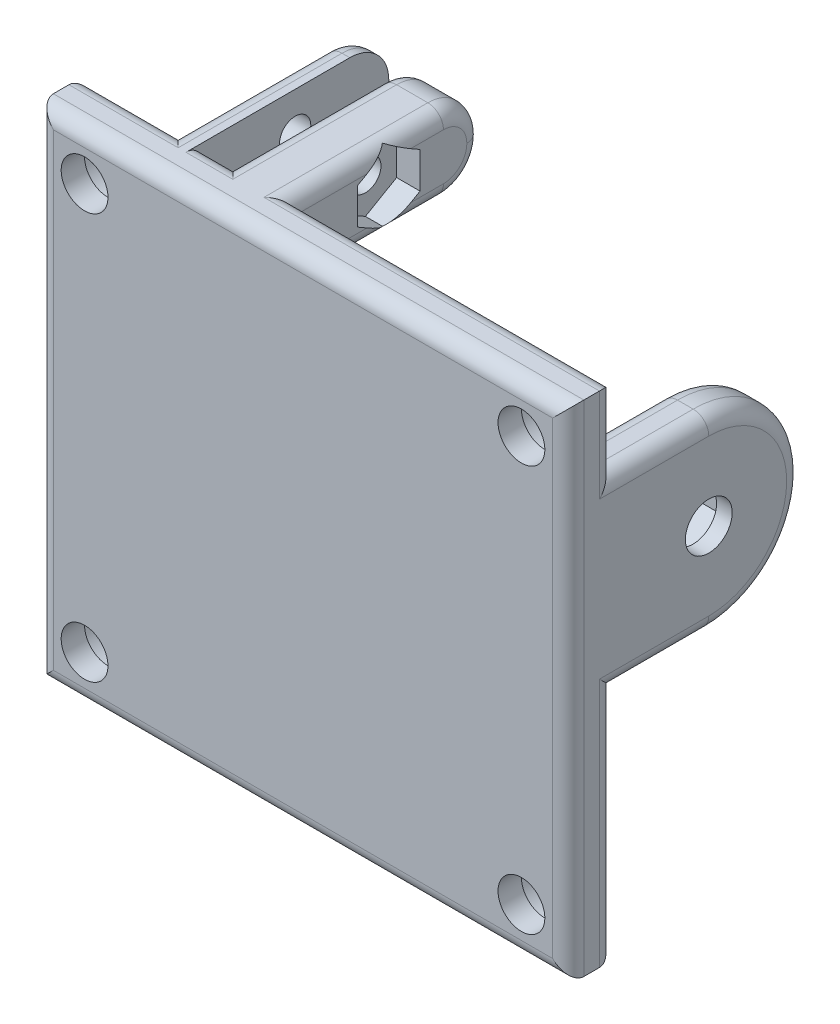
SolidWorks part; units mm, degrees
ref_plane "前视基准面" through (0, 0, 0) normal (0, 0, 1) x (1, 0, 0)
ref_plane "上视基准面" through (0, 0, 0) normal (0, 1, 0) x (1, 0, 0)
ref_plane "右视基准面" through (0, 0, 0) normal (1, 0, 0) x (0, 0, -1)
sketch "草图2" plane through (0, 0, 0) normal (0, 0, 1) x (1, 0, 0)
  line L0 (17, -17) -> (17, 17)
  line L1 (11, -11) -> (-11, -11)
  line L2 (11, -11) -> (11, 11)
  line L3 (11, 11) -> (-11, 11)
  line L4 (-11, -11) -> (-11, 11)
  line L5 (11, -11) -> (-11, 11) construction
  line L6 (11, 11) -> (-11, -11) construction
  line L7 (17, 17) -> (-17, 17)
  line L8 (-17, -17) -> (-17, 17)
  line L9 (17, -17) -> (-17, -17)
  point P0 (0, 0)
  dimension "D1" = 22
  dimension "D2" = 22
  dimension "D3" = 6
extrude "凸台-拉伸2" add sketch "草图2" along normal blind 12
sketch "草图3" plane through (0, 0, 12) normal (0, 0, 1) x (1, 0, 0)
  line L1 (-17, 17) -> (17, 17)
  line L2 (-17, 17) -> (-17, -17)
  line L3 (-17, -17) -> (17, -17)
  line L4 (17, 17) -> (17, -17)
  dimension "D1" = 34
extrude "凸台-拉伸3" add sketch "草图3" along normal blind 3
sketch "草图5" plane through (0, 0, 0) normal (0, 0, -1) x (-1, 0, 0)
  line L1 (-17, 11) -> (17, 11)
  line L2 (-17, 11) -> (-17, -3.5)
  line L3 (-17, -3.5) -> (17, -3.5)
  line L4 (17, 11) -> (17, -3.5)
  line L6 (-17, -17) -> (-17, 17) construction
  line L7 (17, 17) -> (17, -17) construction
  line L9 (-11, 11) -> (11, 11) construction
  dimension "D1" = 14.5
  dimension "D2" = 34
extrude "切除-拉伸1" cut sketch "草图5" against normal blind 12
sketch "草图8" plane through (0, 17, 0) normal (0, 1, 0) x (1, 0, 0)
  line L1 (-17, 0) -> (17, 0)
  line L2 (-17, 0) -> (-17, -15)
  line L3 (-17, -15) -> (17, -15)
  line L4 (17, 0) -> (17, -15)
  dimension "D1" = 15
  dimension "D2" = 34
extrude "凸台-拉伸4" add sketch "草图8" along normal blind 3
sketch "草图9" plane through (0, 0, 0) normal (0, 0, -1) x (-1, 0, 0)
  line L1 (7.5, 20) -> (9.5, 20)
  line L2 (7.5, 20) -> (7.5, 11)
  line L3 (7.5, 11) -> (9.5, 11)
  line L4 (9.5, 20) -> (9.5, 11)
  line L6 (-17, 20) -> (17, 20) construction
  line L7 (-17, 11) -> (17, 11) construction
  line L8 (17, 20) -> (17, 11) construction
  line L9 (0, 0) -> (0, -50000) construction
  line L10 (-7.5, 11) -> (-9.5, 11)
  line L11 (-9.5, 20) -> (-9.5, 11)
  line L12 (-7.5, 20) -> (-9.5, 20)
  line L13 (-7.5, 20) -> (-7.5, 11)
  line L15 (0, 0) -> (-50000, 0) construction
  line L16 (7.5, -11) -> (9.5, -11)
  line L17 (9.5, -20) -> (9.5, -11)
  line L18 (7.5, -20) -> (9.5, -20)
  line L19 (7.5, -20) -> (7.5, -11)
  line L20 (-7.5, -20) -> (-7.5, -11)
  line L21 (-7.5, -20) -> (-9.5, -20)
  line L22 (-9.5, -20) -> (-9.5, -11)
  line L23 (-7.5, -11) -> (-9.5, -11)
  dimension "D1" = 9
  dimension "D2" = 2
  dimension "D3" = 7.5
extrude "切除-拉伸3" cut sketch "草图9" against normal blind 12
sketch "草图10" plane through (-9.5, 0, 0) normal (1, 0, 0) x (0, 0, -1)
  line L0 (0, -17) -> (0, -11) construction
  line L1 (-12, -11) -> (0, -11) construction
  circle A0 centre (-5.9791, -13.5) radius 1
  point P4 (0, -14)
  dimension "D1" = 6
  dimension "D2" = 2.5
  dimension "D3" = 2
extrude "切除-拉伸4" cut sketch "草图10" against normal through all both and the other way through all
sketch "草图11" plane through (-9.5, 0, 0) normal (1, 0, 0) x (0, 0, -1)
  line L0 (-12, 11) -> (0, 11) construction
  line L1 (0, 11) -> (0, 20) construction
  circle A0 centre (-6, 13.5) radius 1
  dimension "D1" = 2
  dimension "D2" = 2.5
  dimension "D3" = 6
extrude "切除-拉伸5" cut sketch "草图11" against normal through all both and the other way through all
sketch "草图12" plane through (0, 0, 0) normal (0, 0, -1) x (-1, 0, 0)
  line L1 (-17, 20) -> (17, 20)
  line L2 (-17, 20) -> (-17, 16)
  line L3 (-17, 16) -> (17, 16)
  line L4 (17, 20) -> (17, 16)
  line L5 (17, 20) -> (17, 11) construction
  line L8 (-17, -17) -> (17, -17)
  line L9 (-17, -17) -> (-17, -16)
  line L10 (-17, -16) -> (17, -16)
  line L11 (17, -17) -> (17, -16)
  line L12 (17, -3.5) -> (17, -17) construction
  line L15 (-17, -3.5) -> (-11, -3.5) construction
  line L16 (-14, -3.5) -> (14, -3.5)
  line L17 (-14, -3.5) -> (-14, -11)
  line L18 (-14, -11) -> (14, -11)
  line L19 (14, -3.5) -> (14, -11)
  line L20 (-17, -17) -> (-17, -3.5) construction
  dimension "D1" = 4
  dimension "D2" = 34
  dimension "D3" = 1
  dimension "D4" = 34
  dimension "D5" = 7.5
  dimension "D6" = 28
  dimension "D7" = 3
extrude "切除-拉伸6" cut sketch "草图12" against normal through all
sketch "草图13" plane through (0, 0, 15) normal (0, 0, 1) x (1, 0, 0)
  line L1 (-14, -3.5) -> (14, -3.5)
  line L2 (-14, -3.5) -> (-14, -11)
  line L3 (-14, -11) -> (14, -11)
  line L4 (14, -3.5) -> (14, -11)
  dimension "D1" = 7.5
  dimension "D2" = 28
extrude "凸台-拉伸5" add sketch "草图13" against normal blind 3
sketch "草图14" plane through (0, 0, 0) normal (0, 0, -1) x (-1, 0, 0)
  line L1 (-17, 16) -> (-11, 16)
  line L2 (-17, 16) -> (-17, 11)
  line L3 (-17, 11) -> (-11, 11)
  line L4 (-11, 16) -> (-11, 11)
  line L7 (-17, 11) -> (-17, 16) construction
  line L8 (-17, 16) -> (-9.5, 16) construction
  line L9 (-17, 11) -> (-9.5, 11) construction
  line L11 (17, 16) -> (11, 16)
  line L12 (17, 16) -> (17, 11)
  line L13 (17, 11) -> (11, 11)
  line L14 (11, 16) -> (11, 11)
  line L15 (9.5, 11) -> (17, 11) construction
  line L31 (-17, -16) -> (-11, -16)
  line L32 (-17, -16) -> (-17, -11)
  line L33 (-17, -11) -> (-11, -11)
  line L34 (-11, -16) -> (-11, -11)
  line L35 (-9.5, -11) -> (-14, -11) construction
  line L37 (17, -16) -> (11, -16)
  line L38 (17, -16) -> (17, -11)
  line L39 (17, -11) -> (11, -11)
  line L40 (11, -16) -> (11, -11)
  line L41 (14, -11) -> (9.5, -11) construction
  line L43 (-3.5, 16) -> (3.5, 16)
  line L44 (-3.5, 16) -> (-3.5, 11)
  line L45 (-3.5, 11) -> (3.5, 11)
  line L46 (3.5, 16) -> (3.5, 11)
  line L48 (-7.5, 16) -> (7.5, 16) construction
  line L49 (-7.5, 11) -> (7.5, 11) construction
  line L50 (-7.5, 11) -> (-7.5, 16) construction
  line L52 (0, 0) -> (-50000, 0) construction
  line L53 (-3.5, -11) -> (3.5, -11)
  line L54 (3.5, -16) -> (3.5, -11)
  line L55 (-3.5, -16) -> (3.5, -16)
  line L56 (-3.5, -16) -> (-3.5, -11)
  point P48 (-3.5, 13.5)
  dimension "D1" = 5
  dimension "D2" = 6
  dimension "D3" = 5
  dimension "D4" = 6
  dimension "D5" = 5
  dimension "D6" = 6
  dimension "D7" = 5
  dimension "D8" = 6
  dimension "D9" = 5
  dimension "D10" = 7
  dimension "D11" = 4
extrude "切除-拉伸7" cut sketch "草图14" against normal blind 12
ref_plane "基准面1" through (0, 0, 0) normal (1, 0, 0) x (0, 0, -1)
sketch "草图15" plane through (0, 0, 0) normal (1, 0, 0) x (0, 0, -1)
  line L0 (-12, 16) -> (-12, -3.5) construction
  line L1 (-6, 11.1906) -> (-4, 12.3453)
  line L2 (-4, 12.3453) -> (-4, 14.6547)
  line L3 (-4, 14.6547) -> (-6, 15.8094)
  line L4 (-6, 15.8094) -> (-8, 14.6547)
  line L5 (-8, 14.6547) -> (-8, 12.3453)
  line L6 (-8, 12.3453) -> (-6, 11.1906)
  line L7 (-3.9791, -12.3453) -> (-5.9791, -11.1906)
  line L8 (-5.9791, -11.1906) -> (-7.9791, -12.3453)
  line L9 (-7.9791, -12.3453) -> (-7.9791, -14.6547)
  line L10 (-7.9791, -14.6547) -> (-5.9791, -15.8094)
  line L11 (-5.9791, -15.8094) -> (-3.9791, -14.6547)
  line L12 (-3.9791, -14.6547) -> (-3.9791, -12.3453)
  circle A0 centre (-6, 13.5) radius 2 construction
  circle A1 centre (-5.9791, -13.5) radius 2 construction
  dimension "D1" = 4
  dimension "D2" = 4
extrude "切除-拉伸8" cut sketch "草图15" against normal blind 5 and the other way blind 5
sketch "草图20" plane through (0, 0, 12) normal (0, 0, -1) x (-1, 0, 0)
  line L0 (0, 0) -> (0, -50000) construction
  line L1 (0, 0) -> (-50000, 0) construction
sketch "草图24" plane through (3.5, 0, 0) normal (-1, 0, 0) x (0, 0, 1)
  line L1 (12, 16) -> (0, 16)
  line L2 (12, 16) -> (12, 11)
  line L3 (12, 11) -> (0, 11)
  line L4 (0, 16) -> (0, 11)
  line L5 (12, -11) -> (0, -11)
  line L6 (12, -11) -> (12, -16)
  line L7 (12, -16) -> (0, -16)
  line L8 (0, -11) -> (0, -16)
  dimension "D1" = 5
  dimension "D2" = 12
  dimension "D3" = 5
  dimension "D4" = 12
extrude "切除-拉伸11" cut sketch "草图24" against normal blind 47.5
sketch "草图25" plane through (0, -3.5, 0) normal (0, 1, 0) x (1, 0, 0)
  line L1 (14, 0) -> (17, 0)
  line L2 (14, 0) -> (14, -12)
  line L3 (14, -12) -> (17, -12)
  line L4 (17, 0) -> (17, -12)
  dimension "D1" = 12
  dimension "D2" = 3
extrude "凸台-拉伸6" add sketch "草图25" along normal blind 15
sketch "草图26" plane through (14, 0, 0) normal (-1, 0, 0) x (0, 0, 1)
  line L0 (6, 13.5) -> (-32.6474, -49986.4851) construction
  circle A1 centre (5.9934, 5) radius 1.5
  dimension "D2" = 3
extrude "切除-拉伸12" cut sketch "草图26" against normal through all
sketch "草图27" plane through (14, 0, 0) normal (-1, 0, 0) x (0, 0, 1)
  line L1 (5.9934, 7.8868) -> (3.4934, 6.4434)
  line L2 (3.4934, 6.4434) -> (3.4934, 3.5566)
  line L3 (3.4934, 3.5566) -> (5.9934, 2.1132)
  line L4 (5.9934, 2.1132) -> (8.4934, 3.5566)
  line L5 (8.4934, 3.5566) -> (8.4934, 6.4434)
  line L6 (8.4934, 6.4434) -> (5.9934, 7.8868)
  circle A0 centre (5.9934, 5) radius 2.5 construction
  dimension "D1" = 5
extrude "切除-拉伸13" cut sketch "草图27" against normal blind 2
sketch "草图28" plane through (14, 0, 0) normal (-1, 0, 0) x (0, 0, 1)
  line L1 (12, -3.5) -> (0, -3.5)
  line L2 (12, -3.5) -> (12, -11)
  line L3 (12, -11) -> (0, -11)
  line L4 (0, -3.5) -> (0, -11)
  dimension "D1" = 7.5
  dimension "D2" = 12
extrude "切除-拉伸14" cut sketch "草图28" against normal through all
sketch "草图29" plane through (14, 0, 0) normal (-1, 0, 0) x (0, 0, 1)
  line L0 (12, -0.9934) -> (12, -3.5)
  line L1 (0, 11.5) -> (12, 11.5)
  line L2 (0, 11.5) -> (0, -3.5)
  line L3 (0, -3.5) -> (12, -3.5)
  line L4 (12, 11.5) -> (12, 10.9934)
  line L5 (5.9934, 10.9934) -> (12, 10.9934)
  line L7 (5.9934, -0.9934) -> (12, -0.9934)
  arc A0 (5.9934, 10.9934) -> (5.9934, -0.9934) centre (5.9934, 5) ccw
  line M7 (0, 11.5) -> (0, -3.5)
  line M8 (0, -3.5) -> (12, -3.5)
  line M9 (12, -3.5) -> (12, 11.5)
  line M10 (12, 11.5) -> (0, 11.5)
  dimension "D1" = 15
  dimension "D2" = 12
  dimension "D3" = 11.9869
  dimension "D4" = 6.0066
extrude "切除-拉伸16" cut sketch "草图29" against normal through all contours A0 L5 M9 M10 M7 | A0 L2 L7 M8 M9 region at (14, -1.7179, 5.0491) region at (14, 11.1299, 8.9967)
sketch "草图30" plane through (0, 0, 12) normal (0, 0, -1) x (-1, 0, 0)
  line L2 (0, 0) -> (50000, 0) construction
  line L4 (0, 0) -> (0, 50000) construction
  line L6 (3.5, 16) -> (-17, 16) construction
  line L7 (-17, 16) -> (-17, 10.9934) construction
  circle A4 centre (-14, 13) radius 1.5
  circle A5 centre (-14, -13) radius 1.5
  circle A6 centre (14, -13) radius 1.5
  circle A7 centre (14, 13) radius 1.5
  dimension "D1" = 3
  dimension "D2" = 3
  dimension "D3" = 3
extrude "切除-拉伸17" cut sketch "草图30" against normal through all
fillet "圆角2" radius 2.5 10 edges at (-15.5, -3.5, 0) (-15.5, -11, 0) (-5.5, -11, 0) (-5.5, -16, 0) (-10.25, -16, 0) (-10.25, -11, 0) (-10.25, 16, 0) (-10.25, 11, 0) (-5.5, 11, 0) (-5.5, 16, 0)
sketch "草图33" plane through (0, 0, 12) normal (0, 0, -1) x (-1, 0, 0)
  circle A0 centre (-14, 13) radius 2.25
  circle A1 centre (14, 13) radius 2.25
  circle A2 centre (14, -13) radius 2.25
  circle A3 centre (-14, -13) radius 2.25
  dimension "D1" = 4.5
extrude "切除-拉伸18" cut sketch "草图33" against normal blind 1.5
fillet "圆角4" radius 1 6 edges at (14, -0.9934, 8.9967) (14, 5, 0) (14, 10.9934, 8.9967) (17, -0.9934, 8.9967) (17, 5, 0) (17, 10.9934, 8.9967)
fillet "圆角5" radius 1 4 edges at (0, 16, 15) (17, 0, 15) (0, -16, 15) (-17, 0, 15)
fillet "圆角6" radius 1 16 edges at (-3.5, 11, 7.25) (-3.5, 11.7322, 0.7322) (-3.5, 15.2678, 0.7322) (-7.5, 16, 7.25) (-7.5, 15.2678, 0.7322) (-7.5, 11.7322, 0.7322) (-3.5, 16, 7.25) (-7.5, 11, 7.25) (-7.5, -11, 7.25) (-7.5, -11.7322, 0.7322) (-7.5, -15.2678, 0.7322) (-3.5, -11, 7.25) (-3.5, -11.7322, 0.7322) (-3.5, -15.2678, 0.7322) (-7.5, -16, 7.25) (-3.5, -16, 7.25)
fillet "圆角8" radius 1 10 edges at (-8, -16, 12) (-14, 16, 12) (-8, 16, 12) (6.25, 16, 12) (17, 12.9967, 12) (17, -7.9967, 12) (6.25, -16, 12) (-14, -16, 12) (-17, -13.5, 12) (-17, 6.25, 12)
fillet "圆角9" radius 1 4 edges at (-11, 11, 7.25) (-11, 11.7322, 0.7322) (-11, 15.2678, 0.7322) (-11, 16, 7.75)
fillet "圆角10" radius 1 4 edges at (-11, -11, 7.25) (-11, -11.7322, 0.7322) (-11, -15.2678, 0.7322) (-11, -16, 7.75)
fillet "圆角11" radius 1 10 edges at (-14, -3.5, 7.25) (-14, -4.2322, 0.7322) (-14, -7.25, 0) (-14, -10.2678, 0.7322) (-17, -3.5, 7.75) (-17, -4.2322, 0.7322) (-17, -7.25, 0) (-17, -10.2678, 0.7322) (-14, -11, 7.25) (-17, -11, 7.75)
